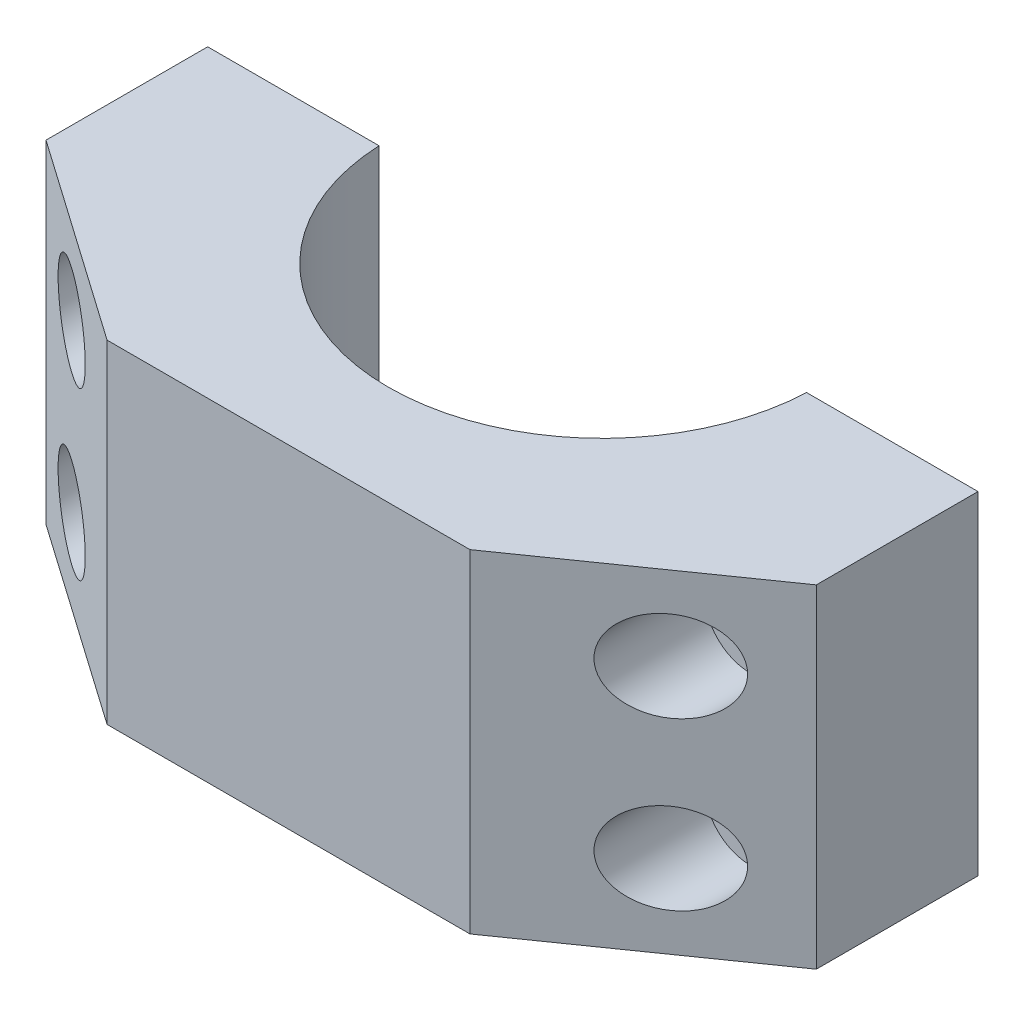
SolidWorks part; units mm, degrees
ref_plane "Alzado" through (0, 0, 0) normal (0, 0, 1) x (1, 0, 0)
ref_plane "Planta" through (0, 0, 0) normal (0, 1, 0) x (1, 0, 0)
ref_plane "Vista lateral" through (0, 0, 0) normal (1, 0, 0) x (0, 0, -1)
sketch "Croquis1" plane through (0, 0, 0) normal (0, 1, 0) x (1, 0, 0)
  line L0 (22.5, 0) -> (40.5, 0)
  line L1 (40.5, 0) -> (40.5, -33)
  line L2 (40.5, -33) -> (-40.5, -33)
  line L3 (-40.5, -33) -> (-40.5, 0)
  line L4 (-40.5, 0) -> (-22.5, 0)
  line L5 (0, 0) -> (0, -33) construction
  arc A0 (-22.5, 0) -> (22.5, 0) centre (0, 0) ccw
  dimension "D2" = 22.5
  dimension "D1" = 81
  dimension "D3" = 33
extrude "Saliente-Extruir1" add sketch "Croquis1" along normal blind 35
sketch "Croquis2" plane through (0, 0, 0) normal (0, 0, -1) x (-1, 0, 0)
  line L0 (-31.5, 35) -> (-31.5, 0) construction
  line L1 (-40.5, 35) -> (-22.5, 35) construction
  line L2 (-40.5, 0) -> (-22.5, 0) construction
  line L3 (0, 0) -> (0, 35) construction
  line L4 (22.5, 35) -> (-22.5, 35) construction
  line L5 (-40.5, 17.5) -> (-22.5, 17.5) construction
  line L6 (-40.5, 35) -> (-40.5, 0) construction
  line L7 (-22.5, 35) -> (-22.5, 0) construction
  circle A0 centre (-31.5, 26.25) radius 2.55
  circle A1 centre (-31.5, 8.75) radius 2.55
  circle A2 centre (31.5, 8.75) radius 2.55
  circle A3 centre (31.5, 26.25) radius 2.55
  dimension "D1" = 5.1
  dimension "D2" = 8.75
extrude "Cortar-Extruir1" cut sketch "Croquis2" against normal up to next
sketch "Croquis3" plane through (0, 0, 33) normal (0, 0, 1) x (1, 0, 0)
  circle A0 centre (-31.5, 26.25) radius 4.75
  circle A1 centre (-31.5, 8.75) radius 4.75
  circle A2 centre (31.5, 26.25) radius 4.75
  circle A3 centre (31.5, 8.75) radius 4.75
  dimension "D1" = 9.5
extrude "Cortar-Extruir2" cut sketch "Croquis3" against normal blind 17
chamfer "Chaflán1" distance 15 angle 55 2 edges at (40.5, 17.5, 33) (-40.5, 17.5, 33)
sketch "Croquis4" plane through (0, 35, 0) normal (0, 1, 0) x (1, 0, 0)
  line L0 (40.5, -18) -> (40.5, 0) construction
  line L1 (-40.5, 0) -> (40.5, 0)
  line L2 (-40.5, 0) -> (-40.5, -1)
  line L3 (-40.5, -1) -> (40.5, -1)
  line L4 (40.5, 0) -> (40.5, -1)
  dimension "D1" = 1
extrude "Cortar-Extruir3" cut sketch "Croquis4" against normal up to next
